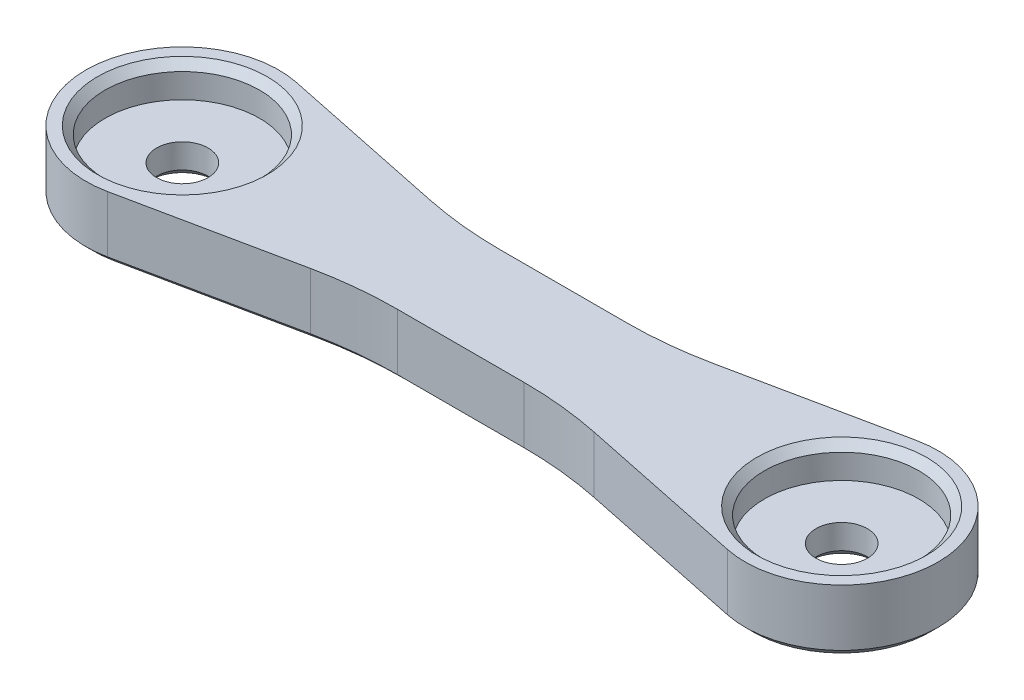
SolidWorks part; units mm, degrees
material "PLA"
ref_plane "Front Plane" through (0, 0, 0) normal (0, 0, 1) x (1, 0, 0)
ref_plane "Top Plane" through (0, 0, 0) normal (0, 1, 0) x (1, 0, 0)
ref_plane "Right Plane" through (0, 0, 0) normal (1, 0, 0) x (0, 0, -1)
sketch "Sketch1" plane through (0, 0, 0) normal (0, 1, 0) x (1, 0, 0)
  line L0 (-8, 4) -> (8, 4)
  line L1 (-25.625, -3) -> (25.625, -3) construction
  line L2 (-25.625, -3) -> (-25.625, 3) construction
  line L3 (-25.625, 3) -> (25.625, 3) construction
  line L4 (25.625, -3) -> (25.625, 3) construction
  line L5 (-25.625, -3) -> (25.625, 3) construction
  line L6 (-25.625, 3) -> (25.625, -3) construction
  line L7 (8, -4) -> (-8, -4)
  line L8 (-24.1001, 7.3433) -> (-8, 4)
  line L9 (-24.1001, -7.3433) -> (-8, -4)
  line L10 (24.1001, 7.3433) -> (8, 4)
  line L11 (24.1001, -7.3433) -> (8, -4)
  line L12 (0, 4) -> (0, -4) construction
  circle A0 centre (-25.625, 0) radius 7.5 construction
  circle A1 centre (25.625, 0) radius 7.5 construction
  circle A2 centre (-25.625, 0) radius 6
  circle A3 centre (25.625, 0) radius 6
  arc A4 (-24.1001, 7.3433) -> (-24.1001, -7.3433) centre (-25.625, 0) ccw
  arc A5 (24.1001, 7.3433) -> (24.1001, -7.3433) centre (25.625, 0) cw
  circle A6 centre (-25.625, 0) radius 2
  circle A7 centre (25.625, 0) radius 2
  point P0 (0, 0)
  point P26 (0, 0)
  dimension "D1" = 12
  dimension "D2" = 12
  dimension "D3" = 1.5
  dimension "D4" = 1.5
  dimension "D9" = 4
  dimension "D10" = 4
  dimension "D5" = 8
  dimension "D6" = 51.25
  dimension "D7" = 8
extrude "Boss-Extrude1" add sketch "Sketch1" against normal blind 5 contours A6 | A7 | A4 L9 L7 L11 A5 L10 L0 L8 region at (-25.625, 0, 0) region at (25.625, 0, 0)
extrude "Cut-Extrude1" cut sketch "Sketch1<3>" against normal blind 2.5 contours A3 | A2 region at (-31.4553, 0, 0) region at (19.7947, 0, 0)
sketch "Sketch1<3>" plane through (0, 0, 0) normal (0, 1, 0) x (1, 0, 0) same geometry as "Sketch1"
fillet "Fillet1" radius 30 4 edges at (8, -2.5, -4) (-8, -2.5, -4) (8, -2.5, 4) (-8, -2.5, 4)
chamfer "Chamfer1" distance 0.6 angle 45 14 edges at (-33.125, -5, 0) (-17.5589, -5, 5.985) (0, -5, 4) (17.5589, -5, 5.985) (33.125, -5, 0) (17.5589, -5, -5.985) (0, -5, -4) (-17.5589, -5, -5.985) (-25.625, -5, 2) (25.625, -5, 2) (-7.9839, -5, 4.1571) (7.9839, -5, 4.1571) (7.9839, -5, -4.1571) (-7.9839, -5, -4.1571)
chamfer "Chamfer2" distance 0.6 angle 45 2 edges at (25.625, 0, 6) (-25.625, 0, 6)
